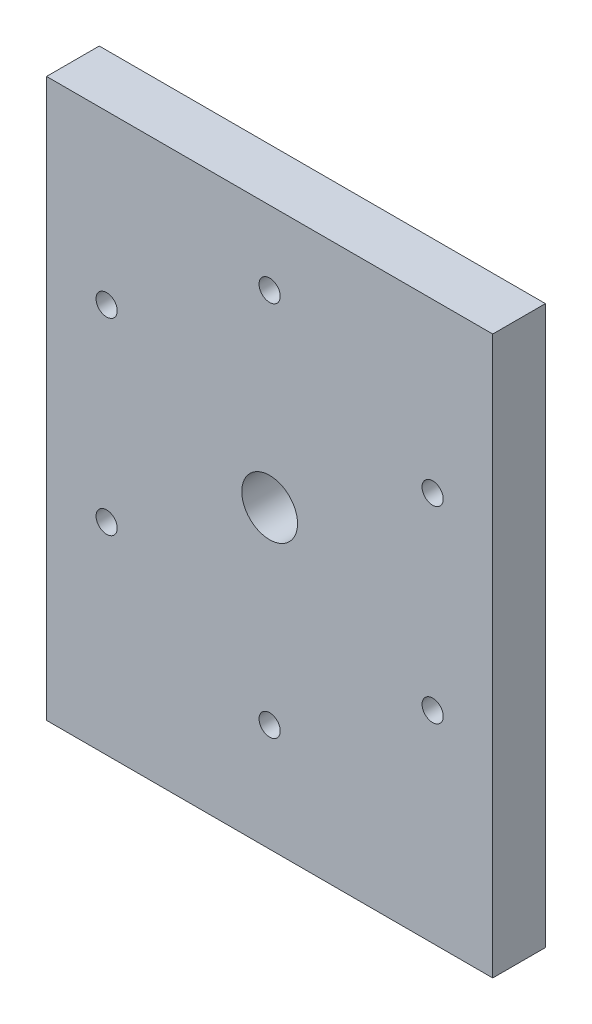
SolidWorks part; units mm, degrees
ref_plane "Front Plane" through (0, 0, 0) normal (0, 0, 1) x (1, 0, 0)
ref_plane "Top Plane" through (0, 0, 0) normal (0, 1, 0) x (1, 0, 0)
ref_plane "Right Plane" through (0, 0, 0) normal (1, 0, 0) x (0, 0, -1)
sketch "Sketch1" plane through (0, 0, 0) normal (0, 0, 1) x (1, 0, 0)
  line L1 (-50.8, 127) -> (50.8, 127)
  line L2 (-50.8, 127) -> (-50.8, 0)
  line L3 (-50.8, 0) -> (50.8, 0)
  line L4 (50.8, 127) -> (50.8, 0)
  circle A0 centre (0, 67.375) radius 6.35
  circle A1 centre (-37.12, 45.9437) radius 2.413
  circle A2 centre (37.12, 45.9437) radius 2.413
  circle A3 centre (0, 24.5125) radius 2.413
  circle A4 centre (-37.12, 88.8062) radius 2.413
  circle A5 centre (37.12, 88.8062) radius 2.413
  circle A6 centre (0, 110.2375) radius 2.413
  dimension "D1" = 127
  dimension "D3" = 12.7
  dimension "D4" = 42.8625
  dimension "D6" = 4.826
  dimension "D7" = 4.826
  dimension "D8" = 4.826
  dimension "D9" = 4.826
  dimension "D10" = 4.826
  dimension "D11" = 4.826
  dimension "D2" = 101.6
  dimension "D5" = 67.375
extrude "Boss-Extrude1" add sketch "Sketch1" along normal blind 12
